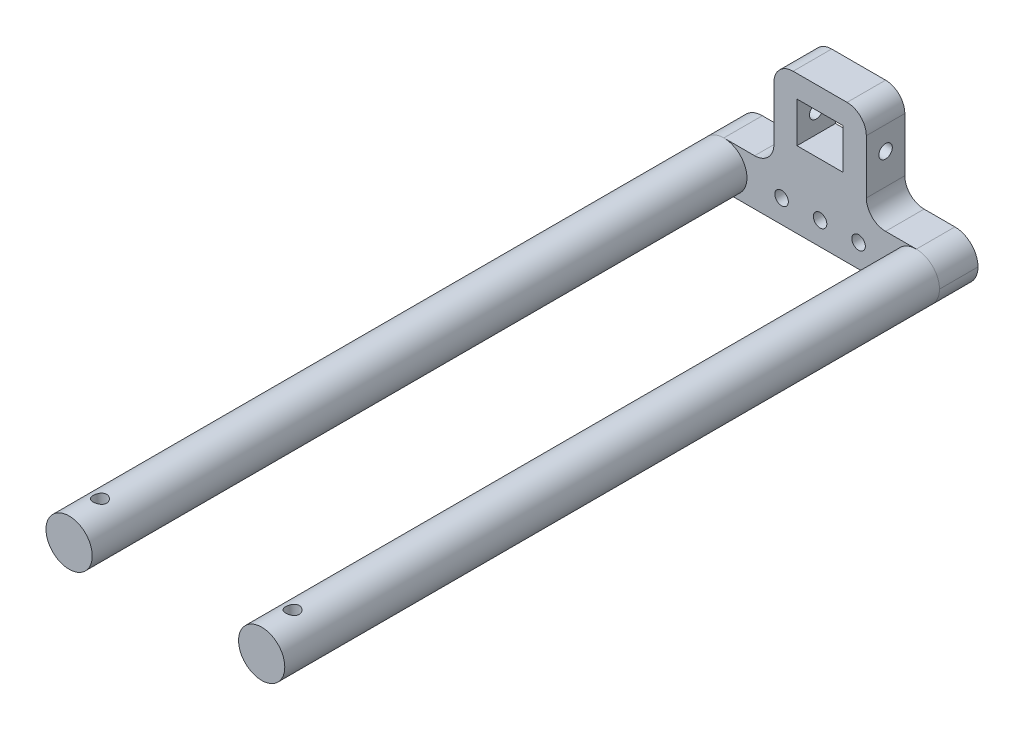
SolidWorks part; units mm, degrees
ref_plane "Front Plane" through (0, 0, 0) normal (0, 0, 1) x (1, 0, 0)
ref_plane "Top Plane" through (0, 0, 0) normal (0, 1, 0) x (1, 0, 0)
ref_plane "Right Plane" through (0, 0, 0) normal (1, 0, 0) x (0, 0, -1)
sketch "Sketch1" plane through (0, 0, 0) normal (0, 0, 1) x (1, 0, 0)
  line L1 (-31, 6) -> (31, 6)
  line L2 (-31, 6) -> (-31, -6)
  line L3 (-31, -6) -> (31, -6)
  line L4 (31, 6) -> (31, -6)
  line L5 (-31, 6) -> (31, -6) construction
  line L6 (-31, -6) -> (31, 6) construction
  point P0 (0, 0)
  dimension "D1" = 62
  dimension "D2" = 12
extrude "Boss-Extrude1" add sketch "Sketch1" along normal blind 10
sketch "Sketch2" plane through (0, 0, 10) normal (0, 0, 1) x (1, 0, 0)
  circle A0 centre (-25, 0) radius 6
  circle A1 centre (25, 0) radius 6
  dimension "D3" = 12
  dimension "D1" = 25
  dimension "D2" = 25
extrude "Boss-Extrude2" add sketch "Sketch2" along normal blind 170
sketch "Sketch3" plane through (0, 6, 0) normal (0, 1, 0) x (1, 0, 0)
  line L0 (31, 0) -> (-31, 0) construction
  line L1 (-12, 0) -> (12, 0)
  line L2 (-12, 0) -> (-12, -10)
  line L3 (-12, -10) -> (12, -10)
  line L4 (12, 0) -> (12, -10)
  line L5 (25, -10) -> (-25, -10) construction
  dimension "D1" = 12
  dimension "D2" = 12
extrude "Boss-Extrude3" add sketch "Sketch3" along normal blind 24
sketch "Sketch4" plane through (0, 0, 0) normal (0, 0, -1) x (-1, 0, 0)
  line L1 (-6, 24.25) -> (6, 24.25)
  line L2 (-6, 24.25) -> (-6, 13.75)
  line L3 (-6, 13.75) -> (6, 13.75)
  line L4 (6, 24.25) -> (6, 13.75)
  line L5 (-6, 24.25) -> (6, 13.75) construction
  line L6 (-6, 13.75) -> (6, 24.25) construction
  point P0 (0, 19)
  dimension "D1" = 10.5
  dimension "D2" = 12
  dimension "D3" = 19
extrude "Cut-Extrude1" cut sketch "Sketch4" against normal up to next
sketch "Sketch5" plane through (12, 0, 0) normal (1, 0, 0) x (0, 0, -1)
  line L0 (0, 30) -> (0, 6) construction
  circle A0 centre (-5, 19) radius 1.75
  dimension "D2" = 3.5
  dimension "D1" = 5
extrude "Cut-Extrude2" cut sketch "Sketch5" against normal through all
fillet "Fillet1" radius 6 4 edges at (-31, -6, 5) (-31, 6, 5) (31, 6, 5) (31, -6, 5)
fillet "Fillet2" radius 5 4 edges at (-12, 6, 5) (12, 6, 5) (-12, 30, 5) (12, 30, 5)
sketch "Sketch6" plane through (0, 0, 0) normal (0, 1, 0) x (1, 0, 0)
  line L0 (-31, -180) -> (-19, -180) construction
  circle A0 centre (-25, -172) radius 1.75
  circle A1 centre (25, -172) radius 1.75
  dimension "D2" = 3.5
  dimension "D1" = 8
extrude "Cut-Extrude3" cut sketch "Sketch6" against normal through all both and the other way through all
sketch "Sketch7" plane through (0, 0, 0) normal (0, 0, -1) x (-1, 0, 0)
  circle A0 centre (-10, 0) radius 1.75
  circle A1 centre (10, 0) radius 1.75
  dimension "D1" = 3.5
  dimension "D2" = 10
  dimension "D3" = 10
extrude "Cut-Extrude4" cut sketch "Sketch7" against normal up to next
sketch "Sketch8" plane through (0, 0, 0) normal (0, 0, -1) x (-1, 0, 0)
  circle A0 centre (0, 0) radius 1.75
  dimension "D1" = 3.5
extrude "Cut-Extrude5" cut sketch "Sketch8" against normal up to next
